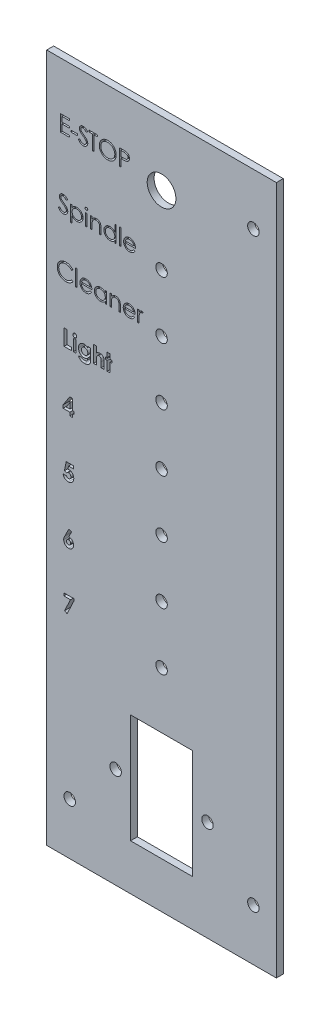
SolidWorks part; units mm, degrees
ref_plane "Front Plane" through (0, 0, 0) normal (0, 0, 1) x (1, 0, 0)
ref_plane "Top Plane" through (0, 0, 0) normal (0, 1, 0) x (1, 0, 0)
ref_plane "Right Plane" through (0, 0, 0) normal (1, 0, 0) x (0, 0, -1)
sketch "Sketch1" plane through (0, 0, 0) normal (0, 0, 1) x (1, 0, 0)
  line L1 (-50, -150) -> (50, -150)
  line L2 (-50, -150) -> (-50, 150)
  line L3 (-50, 150) -> (50, 150)
  line L4 (50, -150) -> (50, 150)
  line L5 (-50, -150) -> (50, 150) construction
  line L6 (-50, 150) -> (50, -150) construction
  point P0 (0, 0)
  dimension "D1" = 300
  dimension "D2" = 100
extrude "Boss-Extrude1" add sketch "Sketch1" along normal blind 3
sketch "Sketch2" plane through (0, 0, 3) normal (0, 0, 1) x (1, 0, 0)
  line L0 (-50, -150) -> (50, -150) construction
  line L5 (-13.5, -130) -> (13.5, -130)
  line L6 (-13.5, -130) -> (-13.5, -82.5)
  line L7 (-13.5, -82.5) -> (13.5, -82.5)
  line L8 (13.5, -130) -> (13.5, -82.5)
  line L9 (0, -1000) -> (0, 49000) construction
  circle A0 centre (20, -106.25) radius 2.5
  circle A1 centre (-20, -106.25) radius 2.5
  point P6 (0, -82.5)
  point P11 (13.5, -106.25)
  dimension "D4" = 20
  dimension "D5" = 5
  dimension "D1" = 47.5
  dimension "D2" = 27
  dimension "D3" = 20
extrude "Cut-Extrude1" cut sketch "Sketch2" against normal up to next
sketch "Sketch3" plane through (0, 0, 3) normal (0, 0, 1) x (1, 0, 0)
  line L0 (0, -1000) -> (0, 49000) construction
  line L1 (50, 150) -> (-50, 150) construction
  line L2 (0, 42) -> (0, 17) construction
  circle A0 centre (0, 122) radius 6.25
  circle A1 centre (0, 92) radius 2.5
  circle A2 centre (0, 67) radius 2.5
  circle A3 centre (0, 42) radius 2.5
  circle A4 centre (0, 17) radius 2.5
  circle A5 centre (0, -8) radius 2.5
  circle A6 centre (0, -33) radius 2.5
  circle A7 centre (0, -58) radius 2.5
  dimension "D1" = 12.5
  dimension "D3" = 5
  dimension "D5" = 25
  dimension "D6" = 25
  dimension "D2" = 28
  dimension "D4" = 30
  dimension "D8" = 25
  dimension "D7" = 5
extrude "Cut-Extrude2" cut sketch "Sketch3" against normal through all
sketch "Sketch4" plane through (0, 0, 3) normal (0, 0, 1) x (1, 0, 0)
  line L0 (0, 122) -> (-50, 122) construction
  line L1 (-50, 150) -> (-50, -150) construction
  line L2 (0, 92) -> (-50, 92) construction
  line L3 (0, 67) -> (-50, 67) construction
  line L4 (0, 42) -> (-50, 42) construction
  line L5 (0, 17) -> (-50, 17) construction
  line L6 (0, -8) -> (-50, -8) construction
  line L7 (0, -33) -> (-50, -33) construction
  line L8 (0, -58) -> (-50, -58) construction
  text T0 "E-STOP     " font "Century Gothic" height 7
  text T1 "Spindle    " font "Century Gothic" height 7
  text T2 "Cleaner   " font "Century Gothic" height 7
  text T3 "<b>Light        </b>" font "Century Gothic" height 7
  text T4 "<b>4</b>              " font "Century Gothic" height 7
  text T5 "<b>5              </b>" font "Century Gothic" height 7
  text T6 "<b>6              </b>" font "Century Gothic" height 7
  text T7 "<b>7              </b>" font "Century Gothic" height 7
  dimension "D2" = 25
  dimension "D1" = 5
extrude "Cut-Extrude3" cut sketch "Sketch4" against normal through all
sketch "Sketch5" plane through (0, 0, 3) normal (0, 0, 1) x (1, 0, 0)
  line L0 (0, -1000) -> (0, 49000) construction
  line L1 (-1000, 0) -> (49000, 0) construction
  line L2 (-50, -150) -> (50, -150) construction
  line L3 (-50, 150) -> (-50, -150) construction
  circle A0 centre (-40, -127.5) radius 2.5
  circle A1 centre (40, -127.5) radius 2.5
  circle A2 centre (40, 127.5) radius 2.5
  dimension "D3" = 5
  dimension "D1" = 22.5
  dimension "D2" = 10
extrude "Cut-Extrude4" cut sketch "Sketch5" against normal through all
